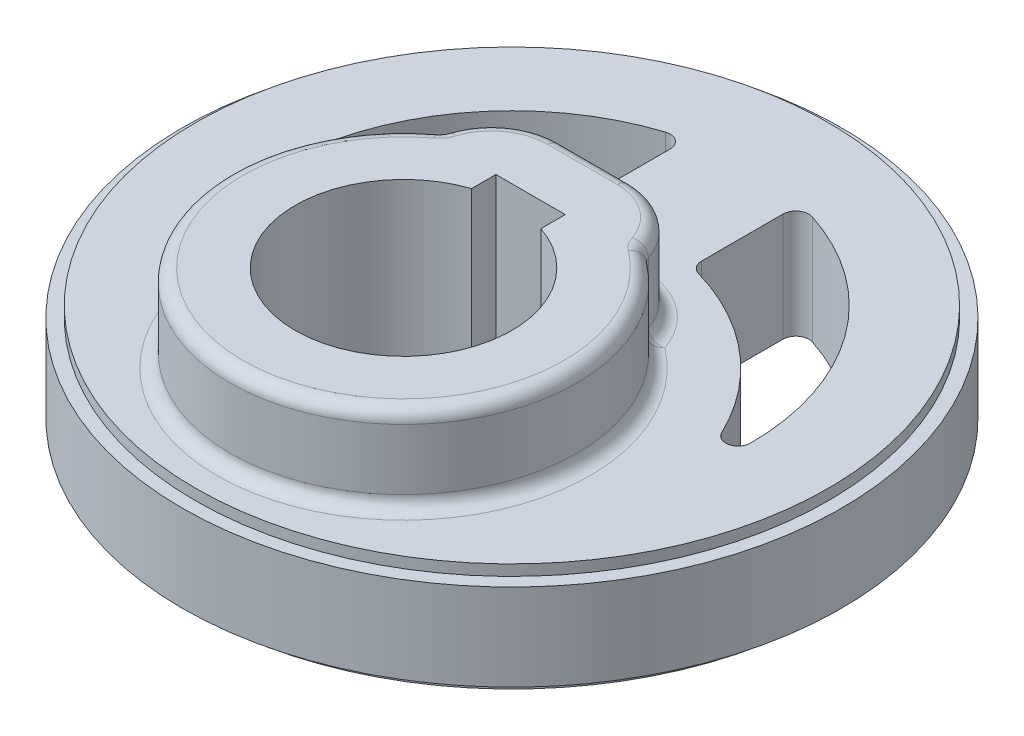
SolidWorks part; units mm, degrees
ref_plane "Front Plane" through (0, 0, 0) normal (0, 0, 1) x (1, 0, 0)
ref_plane "Top Plane" through (0, 0, 0) normal (0, 1, 0) x (1, 0, 0)
ref_plane "Right Plane" through (0, 0, 0) normal (1, 0, 0) x (0, 0, -1)
sketch "Sketch1" plane through (0, 0, 0) normal (0, 1, 0) x (1, 0, 0)
  line L0 (0, -25) -> (0, 0) construction
  line L1 (-8, 4.3) -> (-8, -1.3146)
  line L2 (-8, 4.3) -> (8, 4.3)
  line L3 (8, 4.3) -> (8, -1.3146)
  line L5 (-8, 19.3) -> (8, 19.3)
  line L7 (-23, 19.3) -> (-23, -1.3146) construction
  line L8 (23, 19.3) -> (23, -1.3146) construction
  line L9 (-23, 19.3) -> (23, 19.3) construction
  line L10 (13, 49.4773) -> (13, 30.7494)
  line L11 (-13, 49.4773) -> (-13, 30.7494)
  circle A0 centre (0, 0) radius 76
  circle A1 centre (0, 0) radius 73
  arc A2 (-8, -1.3146) -> (8, -1.3146) centre (0, -25) ccw
  arc A3 (-23.4678, 7.3923) -> (23.4678, 7.3923) centre (0, -25) ccw
  arc A4 (-23.4678, 7.3923) -> (-8, 19.3) centre (-8, 3.3) cw
  arc A5 (23.4678, 7.3923) -> (8, 19.3) centre (8, 3.3) ccw
  arc A6 (15.1724, 27.8658) -> (49.5972, -1.2279) centre (0, -25) cw
  arc A7 (16.9231, 52.3317) -> (55, 0) centre (0, 0) cw
  arc A8 (49.5972, -1.2279) -> (55, 0) centre (52.1591, 0) ccw
  arc A9 (-49.5972, -1.2279) -> (-55, 0) centre (-52.1591, 0) cw
  arc A10 (-15.1724, 27.8658) -> (-49.5972, -1.2279) centre (0, -25) ccw
  arc A11 (-16.9231, 52.3317) -> (-55, 0) centre (0, 0) ccw
  arc A12 (15.1724, 27.8658) -> (13, 30.7494) centre (16, 30.7494) cw
  arc A13 (16.9231, 52.3317) -> (13, 49.4773) centre (16, 49.4773) ccw
  arc A14 (-13, 30.7494) -> (-15.1724, 27.8658) centre (-16, 30.7494) cw
  arc A15 (-13, 49.4773) -> (-16.9231, 52.3317) centre (-16, 49.4773) ccw
  point P13 (0, 4.3)
  point P26 (0, 0)
  point P28 (0, 0)
  point P29 (0, 0)
  point P35 (13, 28.4416)
  point P38 (13, 53.4416)
  point P41 (-13, 28.4416)
  point P44 (-13, 53.4416)
  dimension "D1" = 152
  dimension "D2" = 146
  dimension "D3" = 50
  dimension "D4" = 25
  dimension "D5" = 80
  dimension "D9" = 16
  dimension "D10" = 55
  dimension "D12" = 55
  dimension "D13" = 3
  dimension "D6" = 16
  dimension "D7" = 29.3
  dimension "D11" = 26
  dimension "D8" = 15
extrude "Boss-Extrude1" add sketch "Sketch1" along normal mid plane 25 contours A1 A15 L11 A14 A10 A9 A11 A13 A7 A8 A6 A12 L10 A5 A3 A4 L5 region at (-70.9352, 0, 0)
extrude "Boss-Extrude2" add sketch "Sketch1<3>" along normal mid plane 20 contours A0 A1 region at (-73.8504, 0, 0)
sketch "Sketch1<3>" plane through (0, 0, 0) normal (0, 1, 0) x (1, 0, 0) same geometry as "Sketch1"
extrude "Boss-Extrude3" add sketch "Sketch1<4>" against normal blind 12.5 and the other way blind 32.5 contours A3 A5 L5 A4 A2 L1 L2 L3 region at (0, 0, -18.1378)
sketch "Sketch1<4>" plane through (0, 0, 0) normal (0, 1, 0) x (1, 0, 0) same geometry as "Sketch1"
fillet "Fillet1" radius 3 10 edges at (-23.4678, 22.5, -7.3923) (23.4678, 22.5, -7.3923) (0, 12.5, -19.3) (-17.7602, 12.5, -15.9783) (0, 12.5, 65) (17.7602, 12.5, -15.9783) (-17.7602, 32.5, -15.9783) (17.7602, 32.5, -15.9783) (0, 32.5, 65) (0, 32.5, -19.3)
